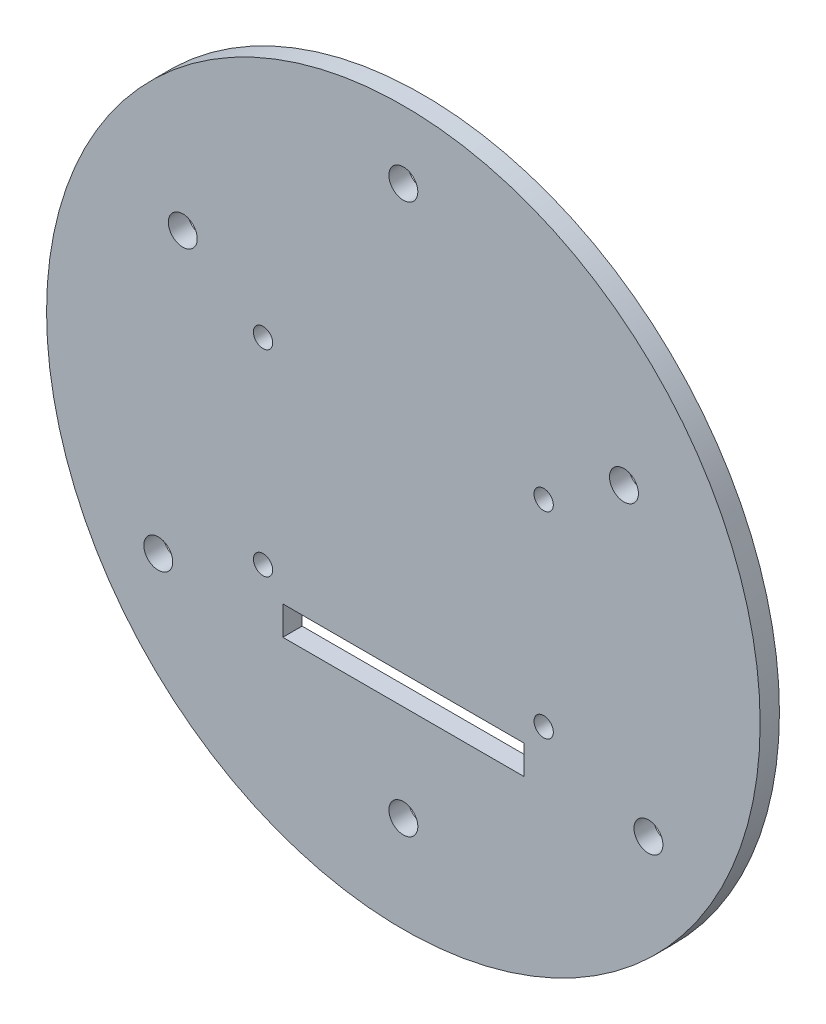
SolidWorks part; units mm, degrees
ref_plane "Plan de face" through (0, 0, 0) normal (0, 0, 1) x (1, 0, 0)
ref_plane "Plan de dessus" through (0, 0, 0) normal (0, 1, 0) x (1, 0, 0)
ref_plane "Plan de droite" through (0, 0, 0) normal (1, 0, 0) x (0, 0, -1)
sketch "Esquisse1" plane through (0, 0, 0) normal (0, 0, 1) x (1, 0, 0)
  line L0 (0, 0) -> (0, -27) construction
  line L1 (0, -27) -> (0, 30) construction
  line L2 (0, 0) -> (25.4165, -15.9375) construction
  line L3 (25.4165, -15.9375) -> (-22.8748, 14.3437) construction
  line L4 (-25.4165, -15.9375) -> (0, 0) construction
  line L5 (0, 0) -> (22.8748, 14.3437) construction
  line L6 (0, 30) -> (25.4165, -15.9375) construction
  line L8 (12.5, -14) -> (-12.5, -14)
  line L9 (12.5, -14) -> (12.5, -17)
  line L10 (12.5, -17) -> (-12.5, -17)
  line L11 (-12.5, -14) -> (-12.5, -17)
  circle A0 centre (0, 0) radius 37
  circle A1 centre (0, 30) radius 1.5
  circle A2 centre (-22.8748, 14.3437) radius 1.5
  circle A3 centre (-25.4165, -15.9375) radius 1.5
  circle A4 centre (0, -27) radius 1.5
  circle A5 centre (25.4165, -15.9375) radius 1.5
  circle A6 centre (22.8748, 14.3437) radius 1.5
  dimension "D1" = 74
  dimension "D11" = 3
  dimension "D12" = 3
  dimension "D13" = 3
  dimension "D14" = 3
  dimension "D15" = 3
  dimension "D16" = 3
  dimension "D2" = 27
  dimension "D3" = 57
  dimension "D4" = 57
  dimension "D5" = 30
  dimension "D6" = 30
  dimension "D7" = 27
  dimension "D8" = 52.5
  dimension "D9" = 52.5
  dimension "D10" = 47.25
  dimension "D17" = 25
  dimension "D18" = 3
  dimension "D19" = 10
  dimension "D20" = 12.5
extrude "Boss.-Extru.1" add sketch "Esquisse1" along normal blind 2
sketch "Esquisse2" plane through (0, 0, 0) normal (0, 0, -1) x (-1, 0, 0)
  line L0 (-16.55, 14.9) -> (-16.55, -13.5)
  line L1 (-12.55, 14.9) -> (12.55, 14.9)
  line L2 (-12.55, 14.9) -> (-12.55, -9.5)
  line L3 (-12.55, -9.5) -> (12.55, -9.5)
  line L4 (12.55, 14.9) -> (12.55, -9.5)
  line L5 (-16.55, -13.5) -> (16.55, -13.5)
  line L6 (16.55, -13.5) -> (16.55, 14.9)
  line L7 (16.55, 14.9) -> (12.55, 14.9)
  line L8 (-16.55, 14.9) -> (-12.55, 14.9)
  point P0 (0, 0)
  dimension "D1" = 25.1
  dimension "D2" = 9.5
  dimension "D3" = 24.4
  dimension "D4" = 4
  dimension "D5" = 4
  dimension "D6" = 4
  dimension "D7" = 12.55
extrude "Boss.-Extru.2" add sketch "Esquisse2" along normal blind 15 contours L8 L0 L5 L6 L7 L4 L3 L2 region at (14.55, 14.4639, 0)
sketch "Esquisse3" plane through (-12.55, 0, 0) normal (1, 0, 0) x (0, 0, -1)
  line L0 (15, 14.9) -> (0, 14.9) construction
  line L1 (10.625, 14.9) -> (8.625, 14.9)
  line L2 (10.625, 14.9) -> (10.625, -13.5)
  line L3 (10.625, -13.5) -> (8.625, -13.5)
  line L4 (8.625, 14.9) -> (8.625, -13.5)
  line L5 (15, -13.5) -> (0, -13.5) construction
  line L6 (0, 14.9) -> (7.5, 14.9) construction
  line L8 (5.625, 14.9) -> (7.625, 14.9)
  line L9 (5.625, 14.9) -> (5.625, -13.5)
  line L10 (5.625, -13.5) -> (7.625, -13.5)
  line L11 (7.625, 14.9) -> (7.625, -13.5)
  line L12 (8, 14.9) -> (8, -13.5) construction
  dimension "D1" = 2
  dimension "D2" = 0.625
  dimension "D3" = 2
  dimension "D4" = 1
  dimension "D5" = 0.375
  dimension "D6" = 0.5
extrude "Boss.-Extru.3" add sketch "Esquisse3" along normal blind 2.25 contours L11 L10 L9 L8 | L2 L3 L4 L1
sketch "Esquisse5" plane through (12.55, 0, 0) normal (-1, 0, 0) x (0, 0, 1)
  line L1 (-10.625, 14.9) -> (-8.625, 14.9)
  line L2 (-10.625, 14.9) -> (-10.625, -9.5)
  line L3 (-10.625, -9.5) -> (-8.625, -9.5)
  line L4 (-8.625, 14.9) -> (-8.625, -9.5)
  line L5 (-7.625, 14.9) -> (-5.625, 14.9)
  line L6 (-7.625, 14.9) -> (-7.625, -9.5)
  line L7 (-7.625, -9.5) -> (-5.625, -9.5)
  line L8 (-5.625, 14.9) -> (-5.625, -9.5)
extrude "Boss.-Extru.4" add sketch "Esquisse5" along normal blind 2.25
sketch "Esquisse7" plane through (0, 0, -15) normal (0, 0, -1) x (-1, 0, 0)
  line L1 (-16.55, 14.9) -> (16.55, 14.9)
  line L2 (-16.55, 14.9) -> (-16.55, -13.5)
  line L3 (-16.55, -13.5) -> (16.55, -13.5)
  line L4 (16.55, 14.9) -> (16.55, -13.5)
extrude "Boss.-Extru.5" add sketch "Esquisse7" against normal blind 1
sketch "Esquisse8" plane through (0, 0, -15) normal (0, 0, -1) x (-1, 0, 0)
  line L1 (-7.5, 7.5) -> (7.5, 7.5)
  line L2 (-7.5, 7.5) -> (-7.5, -7.5)
  line L3 (-7.5, -7.5) -> (7.5, -7.5)
  line L4 (7.5, 7.5) -> (7.5, -7.5)
  line L5 (-7.5, 7.5) -> (7.5, -7.5) construction
  line L6 (-7.5, -7.5) -> (7.5, 7.5) construction
  point P0 (0, 0)
  dimension "D1" = 15
  dimension "D2" = 15
extrude "Enlèv. mat.-Extru.1" cut sketch "Esquisse8" against normal blind 3 contours L3 L4 L1 L2
sketch "Esquisse9" plane through (0, -13.5, 0) normal (0, -1, 0) x (1, 0, 0)
  line L0 (16.55, 0) -> (-16.55, 0) construction
  line L1 (-10.5, -4.4) -> (10.5, -4.4)
  line L2 (-10.5, -4.4) -> (-10.5, -6.9)
  line L3 (-10.5, -6.9) -> (10.5, -6.9)
  line L4 (10.5, -4.4) -> (10.5, -6.9)
  line L6 (10.5, -4.4) -> (10.5, 0) construction
  line L7 (10.5, 0) -> (-10.5, 0) construction
  line L8 (-10.5, 0) -> (-10.5, -4.4) construction
  point P6 (0, -4.4)
  dimension "D1" = 21
  dimension "D2" = 2.5
  dimension "D3" = 4.4
  dimension "D4" = 0
extrude "Enlèv. mat.-Extru.2" cut sketch "Esquisse9" against normal blind 3 contours L1 L4 L3 L2
sketch "Esquisse10" plane through (0, 0, 2) normal (0, 0, 1) x (1, 0, 0)
  line L0 (16.55, -13.5) -> (-16.55, -13.5) construction
  line L1 (-16.55, -13.5) -> (-16.55, 14.9) construction
  line L2 (16.55, 14.9) -> (16.55, -13.5) construction
  line L3 (16.55, 14.9) -> (12.55, 14.9) construction
  line L4 (-16.55, 14.9) -> (-12.55, 14.9) construction
  circle A0 centre (-14.55, 8.9) radius 1
  circle A1 centre (-14.55, -11.5) radius 1
  circle A2 centre (14.55, -11.5) radius 1
  circle A3 centre (14.55, 8.9) radius 1
  dimension "D1" = 2
  dimension "D2" = 2
  dimension "D3" = 2
  dimension "D4" = 2
  dimension "D5" = 2
  dimension "D6" = 2
  dimension "D7" = 2
  dimension "D8" = 2
  dimension "D9" = 2
  dimension "D10" = 6
  dimension "D11" = 6
  dimension "D12" = 2
extrude "Enlèv. mat.-Extru.3" cut sketch "Esquisse10" against normal blind 19
sketch "Esquisse11" plane through (0, 0, -15) normal (0, 0, -1) x (-1, 0, 0)
  line L1 (16.55, 14.9) -> (-16.55, 14.9)
  line L2 (16.55, 14.9) -> (16.55, -13.5)
  line L3 (16.55, -13.5) -> (-16.55, -13.5)
  line L4 (-16.55, 14.9) -> (-16.55, -13.5)
extrude "Enlèv. mat.-Extru.4" cut sketch "Esquisse11" against normal blind 15
